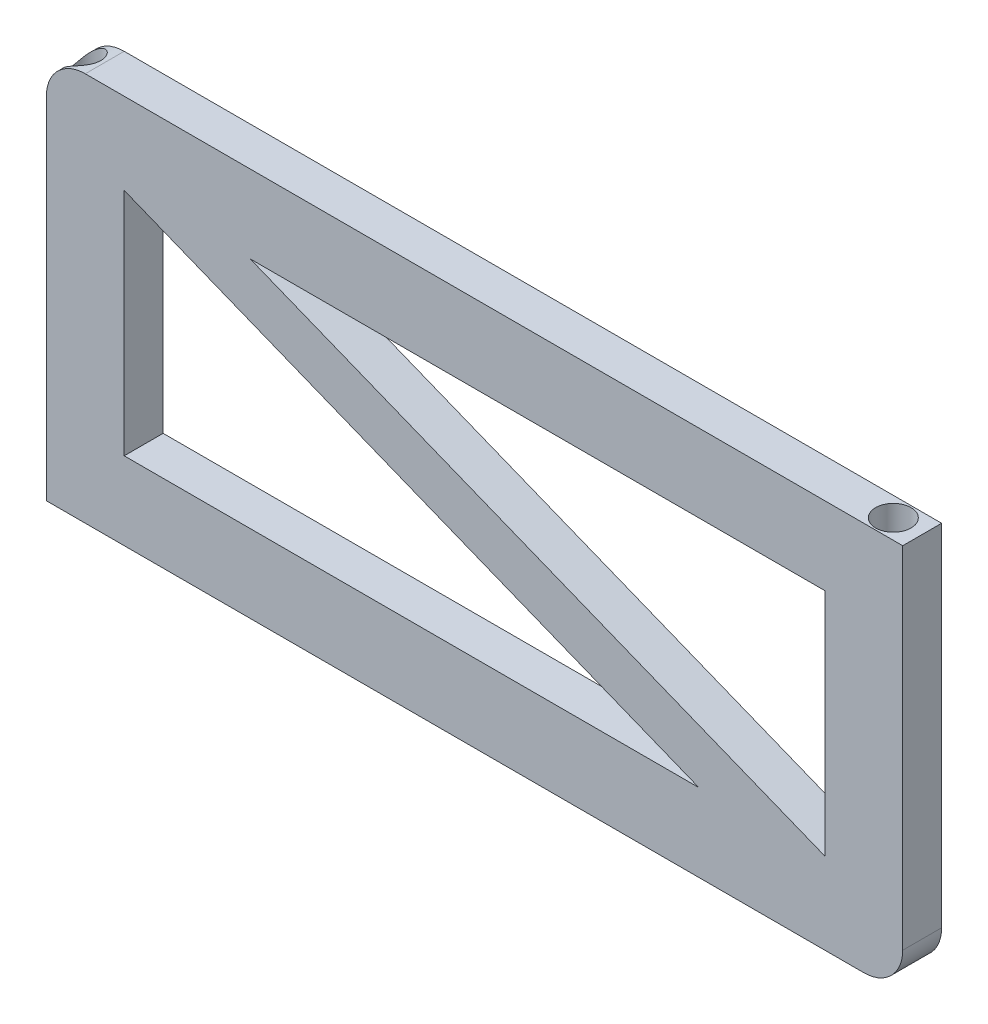
SolidWorks part; units mm, degrees
ref_plane "Front Plane" through (0, 0, 0) normal (0, 0, 1) x (1, 0, 0)
ref_plane "Top Plane" through (0, 0, 0) normal (0, 1, 0) x (1, 0, 0)
ref_plane "Right Plane" through (0, 0, 0) normal (1, 0, 0) x (0, 0, -1)
sketch "Sketch1" plane through (0, 0, 0) normal (0, 0, 1) x (1, 0, 0)
  line L0 (0, 80) -> (200, 0) construction
  line L1 (0, 0) -> (200, 0) construction
  line L2 (0, 0) -> (0, 80) construction
  line L3 (0, 80) -> (200, 80) construction
  line L4 (200, 0) -> (200, 80) construction
  line L5 (-10, -10) -> (-10, 80)
  line L6 (-10, -10) -> (200, -10)
  line L7 (0, 70) -> (190, 70) construction
  line L8 (42.3607, 70) -> (190, 70)
  line L10 (10, 10) -> (10, 69.0557)
  line L11 (10, 10) -> (157.6393, 10)
  line L12 (10, 10) -> (10, 80) construction
  line L13 (0, 90) -> (210, 90)
  line L14 (210, 0) -> (210, 90)
  line L15 (42.3607, 70) -> (190, 10.9443)
  line L16 (10, 69.0557) -> (157.6393, 10)
  line L17 (190, 10.9443) -> (190, 70)
  line L18 (10, 10) -> (200, 10) construction
  line L19 (190, 0) -> (190, 70) construction
  arc A0 (-10, 80) -> (0, 90) centre (0, 80) cw
  arc A1 (200, -10) -> (210, 0) centre (200, 0) ccw
  dimension "D1" = 200
  dimension "D2" = 100
  dimension "D3" = 10
  dimension "D4" = 10
extrude "Boss-Extrude1" add sketch "Sketch1" along normal blind 10
hole_wizard "Ø8.0 (8) Diameter Hole1" positions "Sketch3" profile "Sketch2" hole size "Ø8.0" standard "ANSI Metric" end condition through all
sketch "Sketch3" plane through (0, -10, 0) normal (0, -1, 0) x (-1, 0, 0)
  line L0 (10, -10) -> (10, 0) construction
  line L1 (10, -10) -> (-200, -10) construction
  point P0 (5, -5)
  dimension "D1" = 5
  dimension "D2" = 5
sketch "Sketch2" plane through (-5, -10, 5) normal (1, 0, 0) x (0, 0, -1)
  line L0 (0, 0) -> (0, 100)
  line L1 (0, 100) -> (4, 100)
  line L2 (4, 100) -> (4, 0)
  line L5 (4, 0) -> (0, 0)
  line L11 (0, -6.35) -> (0, 107.95) construction
  dimension "Thru Hole Dia." = 8
  dimension "Thru Hole Depth" = 100
hole_wizard "1/8-27 NPSM Tapped Hole1" positions "Sketch5" profile "Sketch4" tap size "1/8-27 NPSM" standard "ANSI Metric"
sketch "Sketch5" plane through (0, 90, 0) normal (0, 1, 0) x (1, 0, 0)
  line L0 (210, 0) -> (0, 0) construction
  point P0 (202.5859, -5)
  dimension "D1" = 5
sketch "Sketch4" plane through (202.5859, 90, 5) normal (1, 0, 0) x (0, 0, 1)
  line L0 (0, 0) -> (0, 25.7219)
  line L1 (0, 25.7219) -> (4.5466, 22.99)
  line L2 (4.5466, 22.99) -> (4.5466, 0)
  line L5 (4.5466, 0) -> (0, 0)
  line L10 (0, 25.7219) -> (-4.5466, 22.99) construction
  line L11 (0, -6.35) -> (0, 107.95) construction
  dimension "Tap Drill Dia." = 9.0932
  dimension "Tap Drill Depth" = 22.99
  dimension "Drill Angle" = 118
ref_plane "Plane1" through (0, 0, 5) normal (0, 0, 1) x (1, 0, 0)
ref_axis "Axis1" through (532.6952, 70, 5) along (-1, 0, 0)
